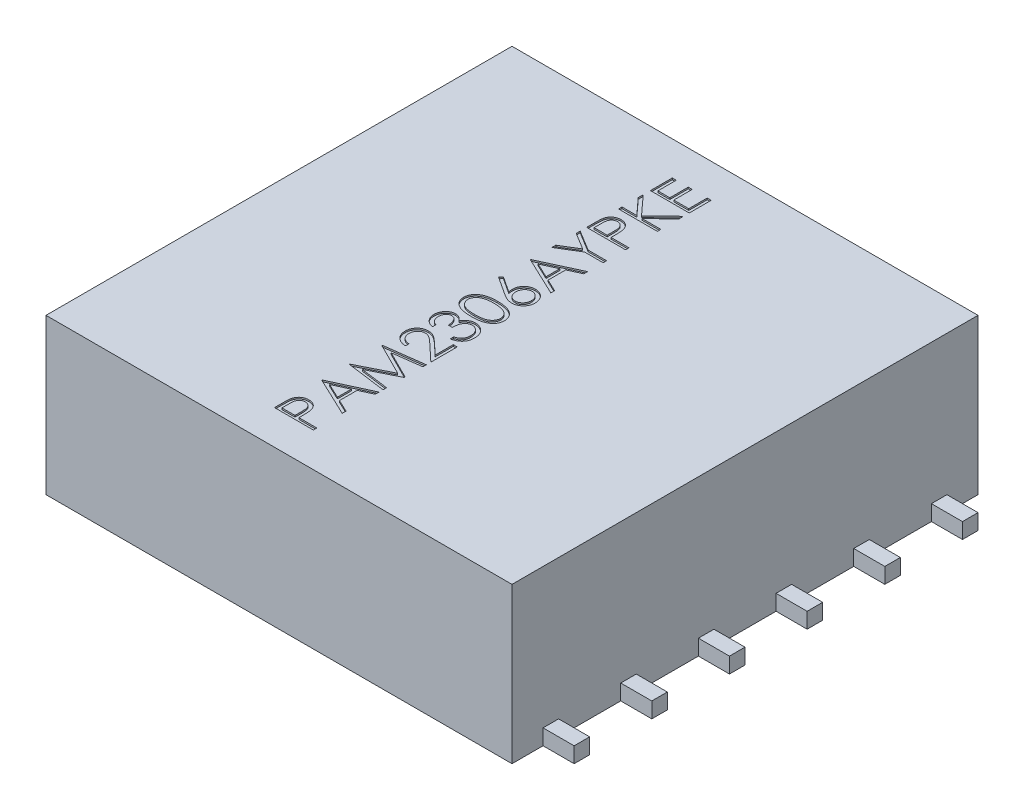
SolidWorks part; units mm, degrees
ref_plane "Front Plane" through (0, 0, 0) normal (0, 0, 1) x (1, 0, 0)
ref_plane "Top Plane" through (0, 0, 0) normal (0, 1, 0) x (1, 0, 0)
ref_plane "Right Plane" through (0, 0, 0) normal (1, 0, 0) x (0, 0, -1)
sketch "BaseS" plane through (0, 0, 0) normal (0, 1, 0) x (1, 0, 0)
  line L1 (-1.5, 1.5) -> (1.5, 1.5)
  line L2 (-1.5, 1.5) -> (-1.5, -1.5)
  line L3 (-1.5, -1.5) -> (1.5, -1.5)
  line L4 (1.5, 1.5) -> (1.5, -1.5)
  line L5 (-1.5, 1.5) -> (1.5, -1.5) construction
  line L6 (-1.5, -1.5) -> (1.5, 1.5) construction
  point P0 (0, 0)
  dimension "W" = 3
  dimension "L" = 3
extrude "Base" add sketch "BaseS" along normal blind 1
sketch "SolderConnectionS" plane through (0, 0, 0) normal (0, 1, 0) x (1, 0, 0)
  line L0 (1.5, -1.25) -> (1.7, -1.25)
  line L1 (1.5, -1.5) -> (1.5, 1.5) construction
  dimension "XDim" = 0.25
  dimension "Length" = 0.2
extrude "SolderConnection" add sketch "SolderConnectionS" along normal blind 0.1 thin thin type mid plane wall 0.1
pattern_linear "SC LP" count 6 spacing 0.5 along (0, 0, -1) of "SolderConnection"
ref_axis "AxisSC" through (0, 0.84, 0) along (0, -1, 0)
pattern_circular "SC CP" count 2 over 360 about axis through (0, 0.84, 0) along (0, -1, 0) of "SolderConnection", "SC LP"
sketch "PartNoS" plane through (0, 1, 0) normal (0, 1, 0) x (1, 0, 0)
  line L0 (0, -1.5) -> (0, 1.5) construction
  line L1 (1.5, 1.5) -> (-1.5, 1.5) construction
  line L4 (-1.5, -1.5) -> (1.5, -1.5) construction
  text T0 "PAM2306AYPKE" font "Century Gothic" height 0.25
extrude "PartNo" cut sketch "PartNoS" against normal blind 0.01
